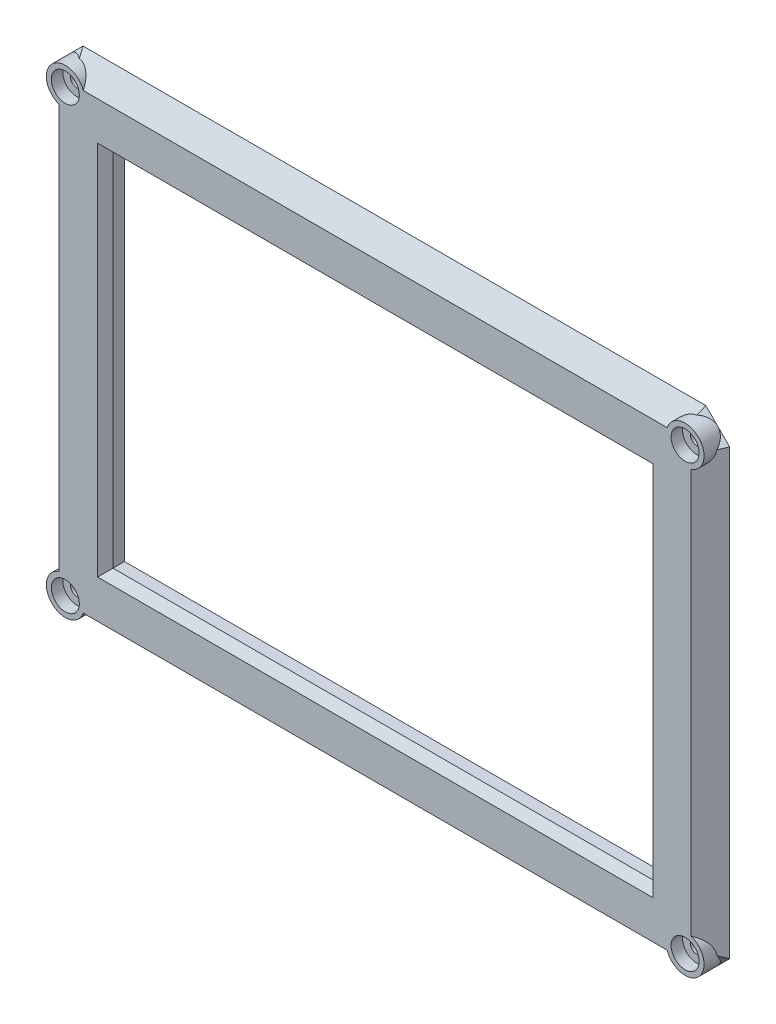
SolidWorks part; units mm, degrees
ref_plane "Front Plane" through (0, 0, 0) normal (0, 0, 1) x (1, 0, 0)
ref_plane "Top Plane" through (0, 0, 0) normal (0, 1, 0) x (1, 0, 0)
ref_plane "Right Plane" through (0, 0, 0) normal (1, 0, 0) x (0, 0, -1)
sketch "Sketch1" plane through (0, 0, 0) normal (0, 0, 1) x (1, 0, 0)
  line L0 (-6.7, 100.5) -> (-147.2, 100.5) construction
  line L1 (-147.2, 100.5) -> (-147.2, 6.7) construction
  line L2 (-6.7, 6.7) -> (-6.7, 100.5) construction
  line L3 (-147.2, 6.7) -> (-6.7, 6.7) construction
  line L4 (-6.7, 100.5) -> (-147.2, 100.5)
  line L5 (-147.2, 100.5) -> (-147.2, 6.7)
  line L6 (-6.7, 6.7) -> (-6.7, 100.5)
  line L7 (-147.2, 6.7) -> (-6.7, 6.7)
  line L8 (-157.9877, -10.2877) -> (4.0877, -10.2877)
  line L9 (4.0877, -10.2877) -> (10.2877, -4.0877)
  line L10 (10.2877, -4.0877) -> (10.2877, 111.2877)
  line L11 (10.2877, 111.2877) -> (4.0877, 117.4877)
  line L12 (4.0877, 117.4877) -> (-157.9877, 117.4877)
  line L13 (-157.9877, 117.4877) -> (-164.1877, 111.2877)
  line L14 (-164.1877, 111.2877) -> (-164.1877, -4.0877)
  line L15 (-164.1877, -4.0877) -> (-157.9877, -10.2877)
  line L16 (-157.9877, -10.2877) -> (4.0877, -10.2877)
  line L17 (4.0877, -10.2877) -> (10.2877, -4.0877)
  line L18 (10.2877, -4.0877) -> (10.2877, 111.2877)
  line L19 (10.2877, 111.2877) -> (4.0877, 117.4877)
  line L20 (4.0877, 117.4877) -> (-157.9877, 117.4877)
  line L21 (-157.9877, 117.4877) -> (-164.1877, 111.2877)
  line L22 (-164.1877, 111.2877) -> (-164.1877, -4.0877)
  line L23 (-164.1877, -4.0877) -> (-157.9877, -10.2877)
  dimension "D1" = 0
extrude "Boss-Extrude1" add sketch "Sketch1" along normal blind 5
chamfer "Chamfer1" distance 5 angle 45 8 edges at (7.1877, 114.3877, 5) (10.2877, 53.6, 5) (7.1877, -7.1877, 5) (-76.95, -10.2877, 5) (-161.0877, -7.1877, 5) (-164.1877, 53.6, 5) (-76.95, 117.4877, 5) (-161.0877, 114.3877, 5)
chamfer "Chamfer2" distance 2 angle 45 4 edges at (-76.95, 6.7, 5) (-6.7, 53.6, 5) (-147.2, 53.6, 5) (-76.95, 100.5, 5)
sketch "Sketch2" plane through (0, 0, 5) normal (0, 0, 1) x (1, 0, 0)
  circle A0 centre (-157.6, -3.7) radius 3.65 construction
  circle A1 centre (-157.6, -3.7) radius 1.65 construction
  circle A2 centre (-157.6, -3.7) radius 3.65
  circle A3 centre (-157.6, -3.7) radius 1.65
  circle A4 centre (-157.6, -3.7) radius 4.9324
  line M9 (-159.1877, 109.2166) -> (-159.1877, -2.0166)
  line M10 (-159.1877, -2.0166) -> (-155.9166, -5.2877)
  line M11 (-155.9166, -5.2877) -> (2.0166, -5.2877)
extrude "Cut-Extrude1" cut sketch "Sketch2" against normal blind 15 contours A3
extrude "Boss-Extrude2" add sketch "Sketch2<3>" against normal up to surface (5 mm away) contours A4 A2 M9 M11 | A3 A2 M10 M9 M11 region at (-159.2858, -1.215, 5) region at (-160.277, -6.377, 5) up to face at (-155.95, -3.7, 0)
sketch "Sketch2<3>" plane through (0, 0, 5) normal (0, 0, 1) x (1, 0, 0) same geometry as "Sketch2"
extrude "Cut-Extrude2" cut sketch "Sketch2<4>" against normal blind 3 contours A3 A2 M10 M11 M9 | A3 A2 M10 M9 M11 region at (-156.2286, -2.3286, 5) region at (-159.2858, -1.215, 5)
sketch "Sketch2<4>" plane through (0, 0, 5) normal (0, 0, 1) x (1, 0, 0) same geometry as "Sketch2"
ref_plane "Plane1" through (-76.95, 0, 0) normal (1, 0, 0) x (0, 0, -1)
ref_plane "Plane2" through (0, 53.6, 0) normal (0, -1, 0) x (-1, 0, 0)
mirror "Mirror1" about plane through (-76.95, 0, 0) normal (1, 0, 0) of "Cut-Extrude2", "Boss-Extrude2", "Cut-Extrude1" second plane through (0, 53.6, 0) second plane normal (0, -1, 0)
